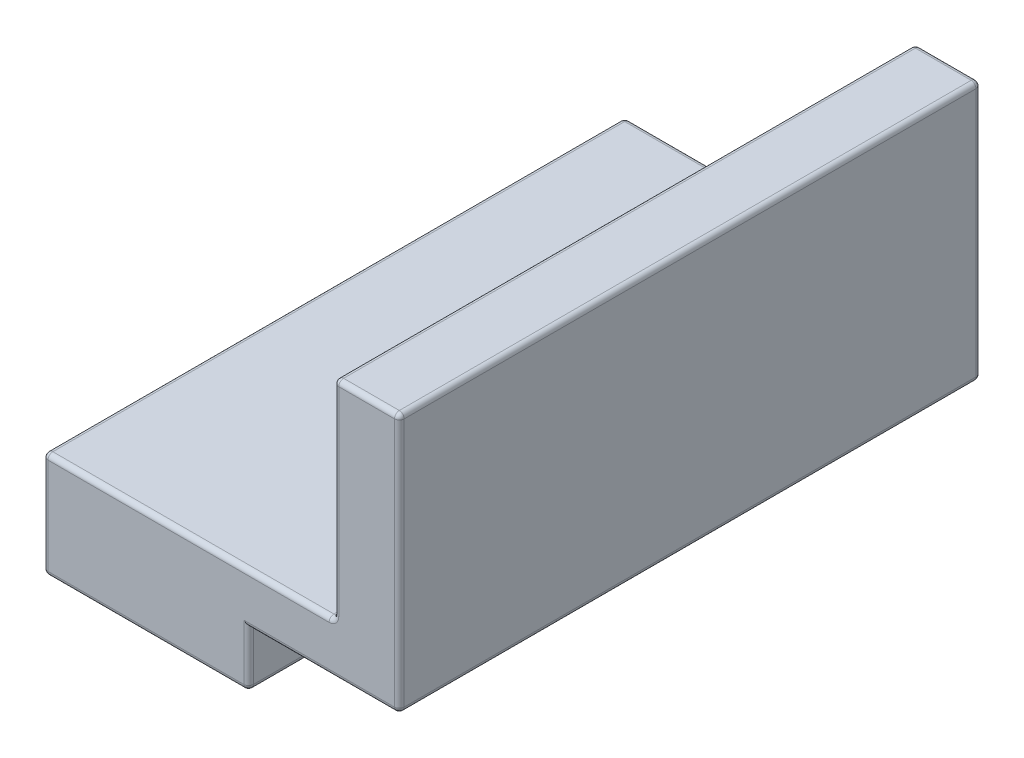
SolidWorks part; units mm, degrees
ref_plane "Front Plane" through (0, 0, 0) normal (0, 0, 1) x (1, 0, 0)
ref_plane "Top Plane" through (0, 0, 0) normal (0, 1, 0) x (1, 0, 0)
ref_plane "Right Plane" through (0, 0, 0) normal (1, 0, 0) x (0, 0, -1)
sketch "Sketch1" plane through (0, 0, 0) normal (0, 0, 1) x (1, 0, 0)
  line L1 (0, 0) -> (735, 0)
  line L2 (735, 0) -> (735, 650)
  line L3 (735, 650) -> (600, 650)
  line L4 (600, 650) -> (600, 218.8)
  line L5 (600, 218.8) -> (0, 218.8)
  line L8 (0, 218.8) -> (0, 0)
  dimension "D1" = 600
  dimension "D3" = 135
  dimension "D4" = 650
  dimension "D5" = 218.8
extrude "Boss-Extrude1" add sketch "Sketch1" along normal blind 1200
sketch "Sketch3" plane through (0, 0, 0) normal (0, 0, -1) x (-1, 0, 0)
  line L1 (-735, 0) -> (-424, 0)
  line L2 (-735, 0) -> (-735, 115)
  line L3 (-735, 115) -> (-424, 115)
  line L4 (-424, 0) -> (-424, 115)
  dimension "D1" = 311
  dimension "D2" = 115
extrude "Cut-Extrude1" cut sketch "Sketch3" against normal up to next
sketch "Sketch2" plane through (0, 0, 0) normal (-1, 0, 0) x (0, 0, 1)
  line L0 (1200, 0) -> (0, 0) construction
  line L1 (20, 198.8) -> (1180, 198.8)
  line L2 (20, 198.8) -> (20, 20)
  line L3 (20, 20) -> (1180, 20)
  line L4 (1180, 198.8) -> (1180, 20)
  line L5 (20, 198.8) -> (1180, 20) construction
  line L6 (20, 20) -> (1180, 198.8) construction
  line L7 (0, 218.8) -> (0, 0) construction
  line L8 (1200, 218.8) -> (1200, 0) construction
  line L9 (1200, 218.8) -> (0, 218.8) construction
  point P0 (600, 109.4)
  dimension "D1" = 20
  dimension "D2" = 20
  dimension "D3" = 20
  dimension "D4" = 20
extrude "Cut-Extrude2" cut sketch "Sketch2" against normal blind 310
sketch "Sketch4" plane through (310, 0, 0) normal (-1, 0, 0) x (0, 0, 1)
  line L0 (1180, 20) -> (1180, 198.8) construction
  line L1 (20, 198.8) -> (1180, 198.8)
  line L2 (20, 198.8) -> (20, 138.8)
  line L3 (20, 138.8) -> (1180, 138.8)
  line L4 (1180, 198.8) -> (1180, 138.8)
  dimension "D1" = 60
extrude "Cut-Extrude3" cut sketch "Sketch4" against normal blind 280
fillet "Fillet2" radius 10 23 edges at (600, 434.4, 1200) (212, 0, 1200) (579.5, 115, 1200) (424, 57.5, 1200) (424, 0, 600) (212, 0, 0) (424, 57.5, 0) (735, 115, 600) (579.5, 115, 0) (735, 382.5, 0) (735, 382.5, 1200) (735, 650, 600) (667.5, 650, 0) (667.5, 650, 1200) (600, 650, 600) (300, 218.8, 1200) (600, 218.8, 600) (600, 434.4, 0) (300, 218.8, 0) (0, 109.4, 1200) (0, 0, 600) (0, 109.4, 0) (0, 218.8, 600)
fillet "Fillet3" radius 2 8 edges at (0, 109.4, 1180) (0, 20, 600) (0, 109.4, 20) (0, 198.8, 600) (295, 198.8, 1180) (295, 198.8, 20) (155, 20, 20) (155, 20, 1180)
